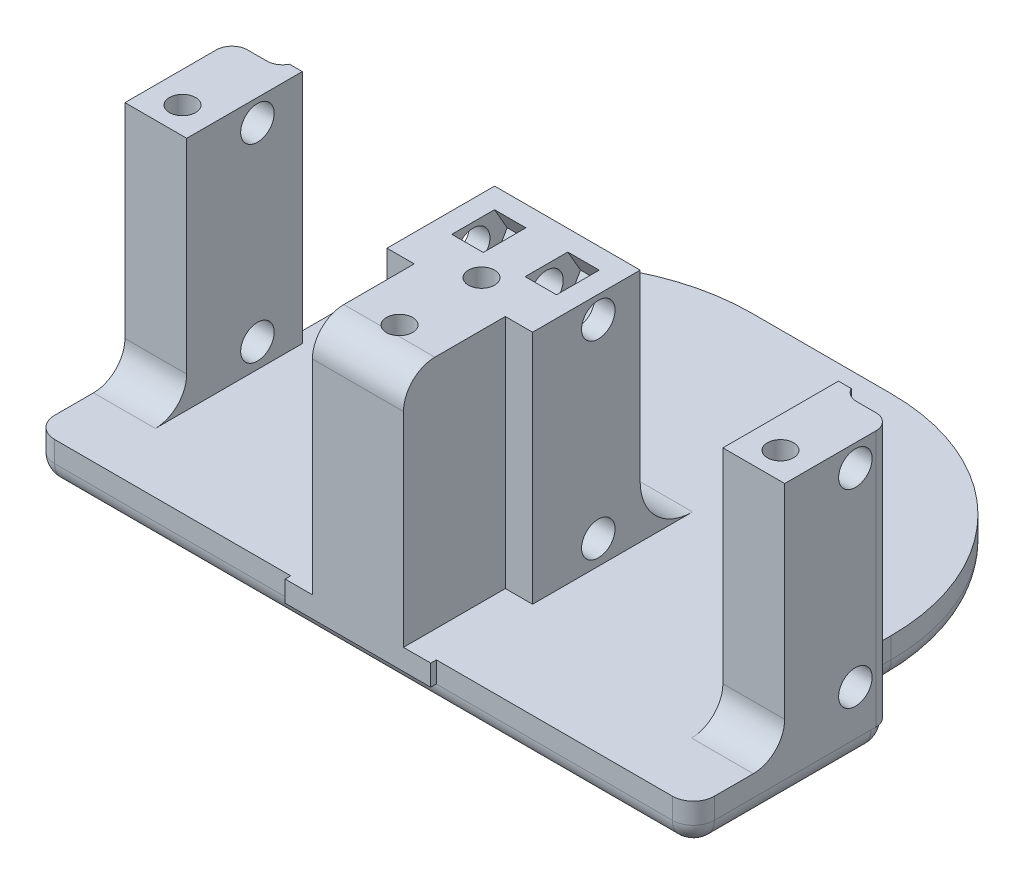
SolidWorks part; units mm, degrees
ref_plane "Alzado" through (0, 0, 0) normal (0, 0, 1) x (1, 0, 0)
ref_plane "Planta" through (0, 0, 0) normal (0, 1, 0) x (1, 0, 0)
ref_plane "Vista lateral" through (0, 0, 0) normal (1, 0, 0) x (0, 0, -1)
sketch "Croquis1" plane through (0, 0, 0) normal (0, 1, 0) x (1, 0, 0)
  line L5 (0, 34.2669) -> (0, 18.57) construction
  line L6 (-31.5, -9.4645) -> (31.5, -9.4645)
  line L8 (-26.6601, 14.2669) -> (-26.6601, 10.9645)
  line L9 (30, 9.4645) -> (28.1601, 9.4645)
  line L11 (26.6601, 14.2669) -> (26.6601, 10.9645)
  line L12 (-31.5, -9.4645) -> (-31.5, 7.9645)
  line L13 (-30, 9.4645) -> (-28.1601, 9.4645)
  line L14 (31.5, -9.4645) -> (31.5, 7.9645)
  line L15 (-31.5, -9.4645) -> (30.7773, 9.2474) construction
  line L16 (-31.5, 9.4645) -> (31.5, -9.4645) construction
  line L17 (0, 0) -> (0, 1.6095) construction
  line L19 (-6.6601, 34.2669) -> (6.6601, 34.2669)
  arc A2 (-26.6601, 14.2669) -> (-6.6601, 34.2669) centre (-6.6601, 14.2669) cw
  arc A3 (-26.6601, 10.9645) -> (-28.1601, 9.4645) centre (-28.1601, 10.9645) cw
  arc A4 (-31.5, 7.9645) -> (-30, 9.4645) centre (-30, 7.9645) cw
  arc A5 (31.5, 7.9645) -> (30, 9.4645) centre (30, 7.9645) ccw
  arc A6 (26.6601, 10.9645) -> (28.1601, 9.4645) centre (28.1601, 10.9645) ccw
  arc A7 (26.6601, 14.2669) -> (6.6601, 34.2669) centre (6.6601, 14.2669) ccw
  point P0 (0, 0)
  point P1 (0, 0)
  point P19 (25.5, 34.8024)
  point P22 (-25.5, 34.8024)
  point P33 (25.5, 34.8024)
  dimension "D3" = 1.5
  dimension "D2" = 20
  dimension "D1" = 63
extrude "Saliente-Extruir1" add sketch "Croquis1" along normal blind 2
sketch "Croquis2" plane through (0, 0, 0) normal (0, 1, 0) x (1, 0, 0)
  line L1 (-6.95, 10) -> (6.95, 10)
  line L2 (-6.95, 10) -> (-6.95, -10)
  line L3 (-6.95, -10) -> (6.95, -10)
  line L4 (6.95, 10) -> (6.95, -10)
  line L5 (-6.95, 10) -> (6.95, -10) construction
  line L6 (-6.95, -10) -> (6.95, 10) construction
  point P0 (0, 0)
  dimension "D1" = 13.9
extrude "Saliente-Extruir2" add sketch "Croquis2" along normal blind 24.5
sketch "Croquis3" plane through (0, 2, 0) normal (0, 1, 0) x (1, 0, 0)
  line L5 (-31.5, 7.9645) -> (-31.5, -9.4645) construction
  line L6 (0, 34.2669) -> (0, 0)
  line L16 (-31.5, 10.2854) -> (-31.5, -0.75)
  line L26 (31.5, -0.75) -> (31.5, 10.2854)
  line L27 (6.6601, 34.2669) -> (-6.6601, 34.2669) construction
  line L28 (31.5, -0.75) -> (25.6, -0.75)
  line L29 (31.5, 10.2854) -> (30.6, 10.2854)
  line L30 (25.6, -0.75) -> (25.6, 10.2854)
  line L31 (25.6, 10.2854) -> (30.6, 10.2854)
  line L33 (25.5, -11.1976) -> (25.5, 0.8024) construction
  line L38 (-31.5, -0.75) -> (-25.6, -0.75)
  line L39 (-25.6, -0.75) -> (-25.6, 10.2854)
  line L40 (-25.5, 0.8024) -> (-25.5, 34.8024) construction
  line L41 (-31.5, 10.2854) -> (-25.6, 10.2854)
  line M36 (31.5, -9.4645) -> (31.5, 7.9645)
  arc M37 (31.5, 7.9645) -> (30, 9.4645) centre (30, 7.9645) ccw
  line M38 (30, 9.4645) -> (28.1601, 9.4645)
  arc M39 (28.1601, 9.4645) -> (26.6601, 10.9645) centre (28.1601, 10.9645) cw
  arc M44 (-26.6601, 10.9645) -> (-28.1601, 9.4645) centre (-28.1601, 10.9645) cw
  line M45 (-28.1601, 9.4645) -> (-30, 9.4645)
  arc M46 (-30, 9.4645) -> (-31.5, 7.9645) centre (-30, 7.9645) ccw
  line M47 (-31.5, 7.9645) -> (-31.5, -9.4645)
  dimension "D1" = 0.1
  dimension "D2" = 5
  dimension "D3" = 0.1
extrude "Saliente-Extruir3" add sketch "Croquis3" along normal blind 22.5 contours L38 L39 M44 M45 M46 M47 | L31 L30 L28 M36 M37 M38 M39 region at (-28.4837, 2, -4.4376) region at (28.4837, 2, -4.4376)
sketch "Croquis4" plane through (-25.5, 0, 0) normal (-1, 0, 0) x (0, 0, 1)
  circle A0 centre (-6.0024, 4.3) radius 1.6
  circle A1 centre (-6.0024, 22.4) radius 1.6
  dimension "D1" = 3.2
  dimension "D2" = 3.2
extrude "Cortar-Extruir1" cut sketch "Croquis4" against normal blind 65.5 and the other way blind 27
fillet "Redondeo1" radius 3 3 edges at (28.55, 2, 0.75) (0, 24.5, 10) (-28.55, 2, 0.75)
fillet "Redondeo2" radius 5 1 edges at (0, 2, -10)
sketch "Croquis7" plane through (0, 24.5, 0) normal (0, 1, 0) x (1, 0, 0)
  line L0 (6.95, 6.0024) -> (-6.95, 6.0024) construction
  line L1 (6.95, 4.4024) -> (6.95, 7.6024) construction
  line L2 (-6.95, 7.6024) -> (-6.95, 4.4024) construction
sketch "Croquis8" plane through (0, 0, 0) normal (1, 0, 0) x (0, 0, -1)
  line L7 (2.7524, 22.4) -> (4.3774, 19.5854)
  line L8 (4.3774, 19.5854) -> (7.6274, 19.5854)
  line L9 (7.6274, 19.5854) -> (9.2524, 22.4)
  line L10 (9.2524, 22.4) -> (7.6274, 25.2146)
  line L11 (7.6274, 25.2146) -> (4.3774, 25.2146)
  line L12 (4.3774, 25.2146) -> (2.7524, 22.4)
  circle A0 centre (6.0024, 22.4) radius 2.8146 construction
  dimension "D1" = 6.5
extrude "Cortar-Extruir3" cut sketch "Croquis8" against normal blind 3 from offset 5
sketch "Croquis9" plane through (0, 0, 0) normal (1, 0, 0) x (0, 0, -1)
  line L1 (2.7524, 22.4) -> (4.3774, 19.5854)
  line L2 (4.3774, 19.5854) -> (7.6274, 19.5854)
  line L3 (7.6274, 19.5854) -> (9.2524, 22.4)
  line L4 (9.2524, 22.4) -> (7.6274, 25.2146)
  line L5 (7.6274, 25.2146) -> (4.3774, 25.2146)
  line L6 (4.3774, 25.2146) -> (2.7524, 22.4)
  circle A0 centre (6.0024, 22.4) radius 2.8146 construction
  dimension "D1" = 6.5
extrude "Cortar-Extruir4" cut sketch "Croquis9" against normal blind 3 from offset 2 offset against normal yes
sketch "Croquis10" plane through (0, 0, 0) normal (1, 0, 0) x (0, 0, -1)
  line L1 (6.0024, 7.55) -> (3.1878, 5.925)
  line L2 (3.1878, 5.925) -> (3.1878, 2.675)
  line L3 (3.1878, 2.675) -> (6.0024, 1.05)
  line L4 (6.0024, 1.05) -> (8.8169, 2.675)
  line L5 (8.8169, 2.675) -> (8.8169, 5.925)
  line L6 (8.8169, 5.925) -> (6.0024, 7.55)
  circle A0 centre (6.0024, 4.3) radius 2.8146 construction
  dimension "D1" = 6.5
extrude "Cortar-Extruir5" cut sketch "Croquis10" against normal blind 3 from offset 1 offset against normal yes
sketch "Croquis11" plane through (0, 0, 0) normal (1, 0, 0) x (0, 0, -1)
  line L1 (2.7524, 4.3) -> (4.3774, 1.4854)
  line L2 (4.3774, 1.4854) -> (7.6274, 1.4854)
  line L3 (7.6274, 1.4854) -> (9.2524, 4.3)
  line L4 (9.2524, 4.3) -> (7.6274, 7.1146)
  line L5 (7.6274, 7.1146) -> (4.3774, 7.1146)
  line L6 (4.3774, 7.1146) -> (2.7524, 4.3)
  circle A0 centre (6.0024, 4.3) radius 2.8146 construction
  dimension "D1" = 6.5
extrude "Cortar-Extruir6" cut sketch "Croquis11" against normal blind 3 from offset 3
sketch "Croquis15" plane through (0, 0, 0) normal (0, -1, 0) x (1, 0, 0)
  line L6 (-31.5, 9.4645) -> (31.5, 9.4645)
  line L7 (31.5, 9.4645) -> (31.5, -7.4891)
  line L8 (29.5, -9.4891) -> (28.6601, -9.4891)
  line L9 (26.6601, -11.4891) -> (26.6601, -14.2669)
  line L10 (6.6601, -34.2669) -> (1.1376, -34.2669)
  line L11 (6.6601, -34.2669) -> (-6.6601, -34.2669) construction
  line L12 (0, 9.4645) -> (0, 4.258) construction
  line L13 (-6.6601, -34.2669) -> (-1.1376, -34.2669)
  line L14 (-26.6601, -11.4891) -> (-26.6601, -14.2669)
  line L15 (-29.5, -9.4891) -> (-28.6601, -9.4891)
  line L16 (-31.5, 9.4645) -> (-31.5, -7.4891)
  line L17 (1.1376, -34.2669) -> (-1.1376, -34.2669)
  arc A0 (28.6601, -9.4891) -> (26.6601, -11.4891) centre (28.6601, -11.4891) ccw
  arc A1 (31.5, -7.4891) -> (29.5, -9.4891) centre (29.5, -7.4891) cw
  arc A2 (26.6601, -14.2669) -> (6.6601, -34.2669) centre (6.6601, -14.2669) cw
  arc A3 (-26.6601, -14.2669) -> (-6.6601, -34.2669) centre (-6.6601, -14.2669) ccw
  arc A4 (-31.5, -7.4891) -> (-29.5, -9.4891) centre (-29.5, -7.4891) ccw
  arc A5 (-28.6601, -9.4891) -> (-26.6601, -11.4891) centre (-28.6601, -11.4891) cw
  dimension "D1" = 2
  dimension "D2" = 20
extrude "Saliente-Extruir5" add sketch "Croquis15" along normal blind 2
sketch "Croquis16" plane through (0, 24.5, 0) normal (0, 1, 0) x (1, 0, 0)
  line L0 (6.95, -0.2744) -> (6.95, -16.6947)
  line L1 (6.95, -9.4645) -> (6.95, 15) construction
  line L2 (6.95, -16.6947) -> (4.35, -16.6947)
  line L3 (4.35, -16.6947) -> (4.35, -0.2744)
  line L4 (4.35, -0.2744) -> (6.95, -0.2744)
  line L5 (0, 0) -> (0, -1.6484)
  line L6 (-4.35, -0.2744) -> (-6.95, -0.2744)
  line L7 (-6.95, -16.6947) -> (-4.35, -16.6947)
  line L8 (-6.95, -0.2744) -> (-6.95, -16.6947)
  line L9 (-4.35, -16.6947) -> (-4.35, -0.2744)
  line M10 (-6.95, 10) -> (-6.95, -7)
  line M11 (-6.95, -7) -> (6.95, -7)
  line M13 (-6.95, -7) -> (6.95, -7)
  line M14 (6.95, -7) -> (6.95, 10)
  dimension "D1" = 2.6
extrude "Cortar-Extruir8" cut sketch "Croquis16" against normal up to surface (22.5 mm away) contours L4 L3 M13 M14 | L3 L2 L0 M13 | L7 L9 L8 M11 | L9 L6 M11 M10 region at (-5.65, 24.5, 11.8473) region at (-5.65, 24.5, 3.6372) region at (5.65, 24.5, 3.6372) region at (5.65, 24.5, 11.8473) up to face at (0, 2, -7.2773)
sketch "Croquis13" plane through (0, 0, 0) normal (0, -1, 0) x (1, 0, 0)
  line L0 (6.95, -6.0024) -> (-6.95, -6.0024) construction
  line L1 (-5, -2.7524) -> (5, -2.7524)
  line L2 (-5, -2.7524) -> (-5, -9.2524)
  line L3 (-5, -9.2524) -> (5, -9.2524)
  line L4 (5, -2.7524) -> (5, -9.2524)
  line L5 (-5, -2.7524) -> (5, -9.2524) construction
  line L6 (-5, -9.2524) -> (5, -2.7524) construction
  point P0 (0, -6.0024)
  dimension "D1" = 6.5
  dimension "D2" = 10
extrude "Cortar-Extruir7" cut sketch "Croquis13" against normal blind 2 and the other way blind 3
fillet "Redondeo6" radius 2 13 edges at (-31.5, -2, 0.9877) (-30.9142, -2, -8.9033) (-29.0801, -2, -9.4891) (-27.2459, -2, -10.0749) (-26.6601, -2, -12.878) (-20.8022, -2, -28.409) (0, -2, -34.2669) (20.8022, -2, -28.409) (26.6601, -2, -12.878) (27.2459, -2, -10.0749) (29.0801, -2, -9.4891) (30.9142, -2, -8.9033) (31.5, -2, 0.9877)
fillet "Redondeo7" radius 2 5 edges at (31.5, 1, 9.4645) (30.9142, -1.4142, 9.4645) (-31.5, 1, 9.4645) (-30.9142, -1.4142, 9.4645) (0, -2, 9.4645)
sketch "Croquis5" plane through (0, 24.5, 0) normal (0, 1, 0) x (1, 0, 0)
  line L1 (0, 0) -> (0, -1.2356) construction
  circle A0 centre (0, 1.7983) radius 1.25
  circle A1 centre (0, -6.0269) radius 1.25
  circle A6 centre (-28.55, 1.7983) radius 1.25
  circle A7 centre (28.55, 1.7983) radius 1.25
  dimension "D1" = 2.5
  dimension "D3" = 2.5
  dimension "D4" = 2.5
  dimension "D2" = 2.5
  dimension "D5" = 2.95
  dimension "D6" = 2.95
extrude "Cortar-Extruir2" cut sketch "Croquis5" against normal blind 83.5
